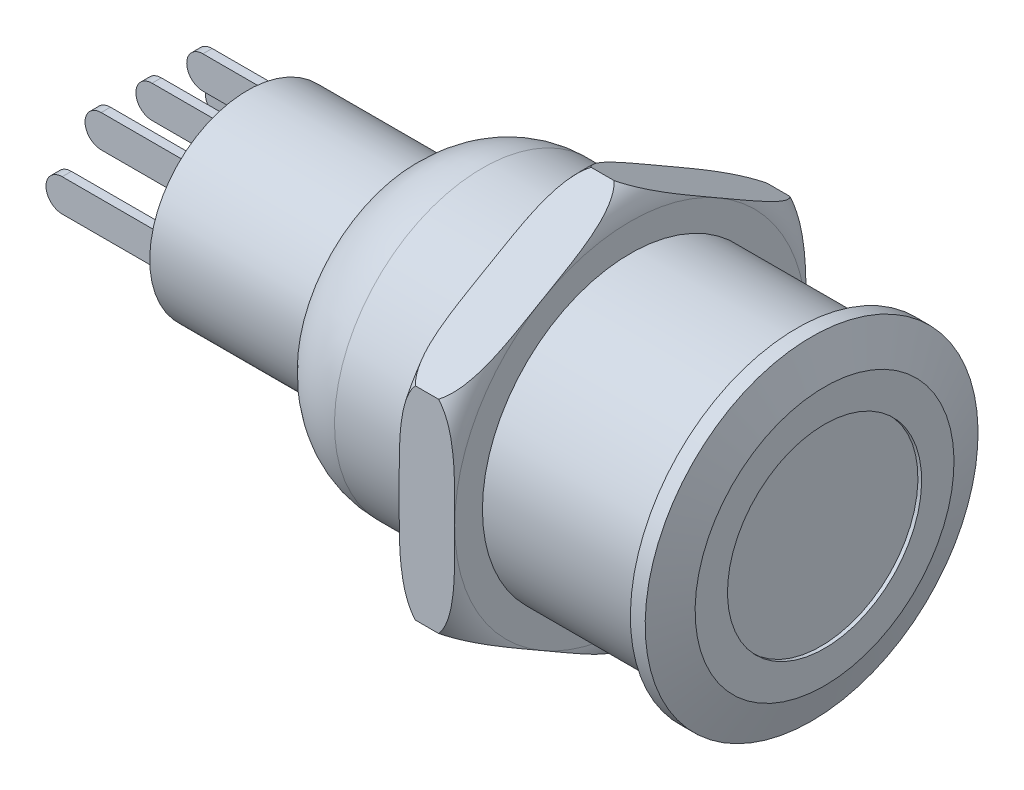
SolidWorks part; units mm, degrees
ref_plane "Front Plane" through (0, 0, 0) normal (0, 0, 1) x (1, 0, 0)
ref_plane "Top Plane" through (0, 0, 0) normal (0, 1, 0) x (1, 0, 0)
ref_plane "Right Plane" through (0, 0, 0) normal (1, 0, 0) x (0, 0, -1)
sketch "Sketch1" plane through (0, 0, 0) normal (0, 0, 1) x (1, 0, 0)
  line L0 (0, 0) -> (0, 7)
  line L2 (-1.5, 9) -> (-1.5, 8)
  line L3 (-1.5, 8) -> (-18.5, 8)
  line L4 (-22.08, 6.43) -> (-22.08, 5.29)
  line L5 (-22.08, 5.29) -> (-31.2, 5.29)
  line L6 (-31.2, 5.29) -> (-31.2, 0)
  line L7 (-31.2, 0) -> (0, 0)
  line L8 (-1.5, 9) -> (-0.7, 9)
  line L9 (-0.7, 9) -> (0, 7)
  arc A0 (-18.5, 8) -> (-22.08, 6.43) centre (-18.5, 3.1333) ccw
  dimension "D1" = 8
  dimension "D2" = 1.5
  dimension "D3" = 9
  dimension "D4" = 29.7
  dimension "D5" = 9.12
  dimension "D6" = 18.5
  dimension "D7" = 5.29
  dimension "D8" = 6.43
  dimension "D9" = 0.8
  dimension "D10" = 7
revolve "Revolve1" add sketch "Sketch1" angle 360 about L7
sketch "Sketch2" plane through (0, 0, 0) normal (1, 0, 0) x (0, 0, -1)
  circle A0 centre (0, 0) radius 5.25
  dimension "D1" = 10.5
extrude "Cut-Extrude1" cut sketch "Sketch2" against normal blind 0.2
sketch "Sketch3" plane through (-31.2, 0, 0) normal (-1, 0, 0) x (0, 0, 1)
  line L0 (0, 0) -> (0, 1.54) construction
  line L1 (-4.56, -0.96) -> (-4.06, -0.96)
  line L2 (-4.56, -0.96) -> (-4.56, 0.79)
  line L3 (-4.56, 0.79) -> (-4.06, 0.79)
  line L4 (-4.06, -0.96) -> (-4.06, 0.79)
  line L5 (-3, 1.54) -> (-2.5, 1.54)
  line L6 (-3, 1.54) -> (-3, 3.29)
  line L7 (-3, 3.29) -> (-2.5, 3.29)
  line L8 (-2.5, 1.54) -> (-2.5, 3.29)
  line L9 (-0.25, 1.54) -> (0.25, 1.54)
  line L10 (-0.25, 1.54) -> (-0.25, 3.29)
  line L11 (-0.25, 3.29) -> (0.25, 3.29)
  line L12 (0.25, 1.54) -> (0.25, 3.29)
  line L13 (2.5, 1.54) -> (3, 1.54)
  line L14 (2.5, 1.54) -> (2.5, 3.29)
  line L15 (2.5, 3.29) -> (3, 3.29)
  line L16 (3, 1.54) -> (3, 3.29)
  line L17 (4.06, -0.96) -> (4.56, -0.96)
  line L18 (4.06, -0.96) -> (4.06, 0.79)
  line L19 (4.06, 0.79) -> (4.56, 0.79)
  line L20 (4.56, -0.96) -> (4.56, 0.79)
  line L21 (-4.06, -0.96) -> (4.06, -0.96) construction
  line L22 (-2.5, 1.54) -> (2.5, 1.54) construction
  line L23 (0, 3.29) -> (0, 5.29) construction
  circle A0 centre (0, 0) radius 5.29 construction
  point P23 (0, -0.96)
  point P24 (0, 1.54)
  dimension "D1" = 1.75
  dimension "D2" = 0.5
  dimension "D3" = 6
  dimension "D4" = 9.12
  dimension "D5" = 4.25
  dimension "D6" = 2
extrude "Boss-Extrude1" add sketch "Sketch3" along normal blind 5.79
sketch "Sketch4" plane through (-31.2, 0, 0) normal (-1, 0, 0) x (0, 0, 1)
  line L0 (4.06, -0.96) -> (4.56, -0.96) construction
  line L1 (4.56, -0.96) -> (4.56, 0.79) construction
  line L2 (4.06, 0.79) -> (4.56, 0.79) construction
  line L3 (4.06, -0.96) -> (4.06, 0.79) construction
  line L4 (-4.56, -0.96) -> (-4.06, -0.96) construction
  line L5 (-4.06, -0.96) -> (-4.06, 0.79) construction
  line L6 (-4.56, 0.79) -> (-4.06, 0.79) construction
  line L7 (-4.56, -0.96) -> (-4.56, 0.79) construction
  line L8 (4.06, -0.96) -> (4.56, -0.96)
  line L9 (4.56, -0.96) -> (4.56, 0.79)
  line L10 (4.06, 0.79) -> (4.56, 0.79)
  line L11 (4.06, -0.96) -> (4.06, 0.79)
  line L12 (-4.56, -0.96) -> (-4.06, -0.96)
  line L13 (-4.06, -0.96) -> (-4.06, 0.79)
  line L14 (-4.56, 0.79) -> (-4.06, 0.79)
  line L15 (-4.56, -0.96) -> (-4.56, 0.79)
extrude "Boss-Extrude2" add sketch "Sketch4" along normal blind 6.34
sketch "Sketch5" plane through (0, 0, -3) normal (0, 0, -1) x (-1, 0, 0)
  line L0 (36.99, 3.29) -> (31.2, 3.29) construction
  line L1 (36.99, 3.29) -> (36.99, 1.54) construction
  line L2 (36.99, 1.54) -> (31.2, 1.54) construction
  line L3 (36.99, 3.29) -> (36.99, 1.54)
  line L4 (36.99, 3.29) -> (36.115, 3.29)
  line L5 (36.99, 1.54) -> (36.115, 1.54)
  arc A0 (36.115, 1.54) -> (36.115, 3.29) centre (36.115, 2.415) ccw
  line M3 (31.2, 1.54) -> (36.99, 1.54)
  line M4 (36.99, 1.54) -> (36.99, 3.29)
  line M5 (36.99, 3.29) -> (31.2, 3.29)
extrude "Cut-Extrude2" cut sketch "Sketch5" against normal through all contours A0 L3 M5 | A0 M3 M4 region at (-36.7946, 1.7354, -3) region at (-36.7946, 3.0946, -3)
sketch "Sketch6" plane through (0, 0, -4.56) normal (0, 0, -1) x (-1, 0, 0)
  line L0 (37.54, 0.79) -> (31.2, 0.79) construction
  line L1 (37.54, -0.96) -> (31.2, -0.96) construction
  line L2 (37.54, 0.79) -> (37.54, -0.96) construction
  line L7 (31.2, 0.79) -> (31.2, -0.96)
  line L8 (31.2, -0.96) -> (37.54, -0.96)
  line L9 (37.54, -0.96) -> (37.54, 0.79)
  line L10 (37.54, 0.79) -> (31.2, 0.79)
  line L12 (36.665, -0.96) -> (37.54, -0.96)
  line L13 (37.54, -0.96) -> (37.54, 0.79)
  line L14 (37.54, 0.79) -> (36.665, 0.79)
  arc A0 (36.665, -0.96) -> (36.665, 0.79) centre (36.665, -0.085) ccw
  line M7 (31.2, -0.96) -> (37.54, -0.96)
  line M8 (37.54, -0.96) -> (37.54, 0.79)
  line M9 (37.54, 0.79) -> (31.2, 0.79)
  dimension "D1" = 0
extrude "Cut-Extrude3" cut sketch "Sketch6" against normal through all contours A0 L13 M9 | A0 M7 M8 region at (-37.3446, 0.5946, -4.56) region at (-37.3446, -0.7646, -4.56)
ref_plane "Plane1" through (-13.5, 0, 0) normal (-1, 0, 0) x (0, 0, 1)
sketch "Sketch7" plane through (-13.5, 0, 0) normal (-1, 0, 0) x (0, 0, 1)
  line L1 (0, 10.9697) -> (-9.5, 5.4848)
  line L2 (-9.5, 5.4848) -> (-9.5, -5.4848)
  line L3 (-9.5, -5.4848) -> (0, -10.9697)
  line L4 (0, -10.9697) -> (9.5, -5.4848)
  line L5 (9.5, -5.4848) -> (9.5, 5.4848)
  line L6 (9.5, 5.4848) -> (0, 10.9697)
  circle A0 centre (0, 0) radius 9.5 construction
  dimension "D1" = 19
extrude "Boss-Extrude3" add sketch "Sketch7" against normal blind 3
sketch "Sketch8" plane through (0, 0, 0) normal (0, 0, 1) x (1, 0, 0)
  line L3 (0, 0) -> (-5.8404, 0) construction
  line L4 (-13.5, 5.4848) -> (-13.5, 10.9697) construction
  line L6 (-10.5, 10.9697) -> (-13.5, 10.9697) construction
  line L7 (-12.625, 10.9697) -> (-11.375, 10.9697)
  line L8 (-10.5, 5.4848) -> (-10.5, 10.9697) construction
  line L9 (-13.5, 8) -> (-18.5, 8) construction
  line L10 (-13.5, 8) -> (-18.5, 8) construction
  line L11 (-13.5, 15) -> (-13.5, 9.5)
  line L13 (-10.5, 9.5) -> (-10.5, 15)
  line L14 (-10.5, 15) -> (-13.5, 15)
  arc A1 (-13.5, 9.5) -> (-12.625, 10.9697) centre (-11.8283, 9.5) cw
  arc A2 (-11.375, 10.9697) -> (-10.5, 9.5) centre (-12.1717, 9.5) cw
  point P10 (-12, 10.9697)
  dimension "D1" = 1.25
  dimension "D2" = 15
  dimension "D3" = 1.5
revolve "Cut-Revolve3" cut sketch "Sketch8" angle 360 about L3
